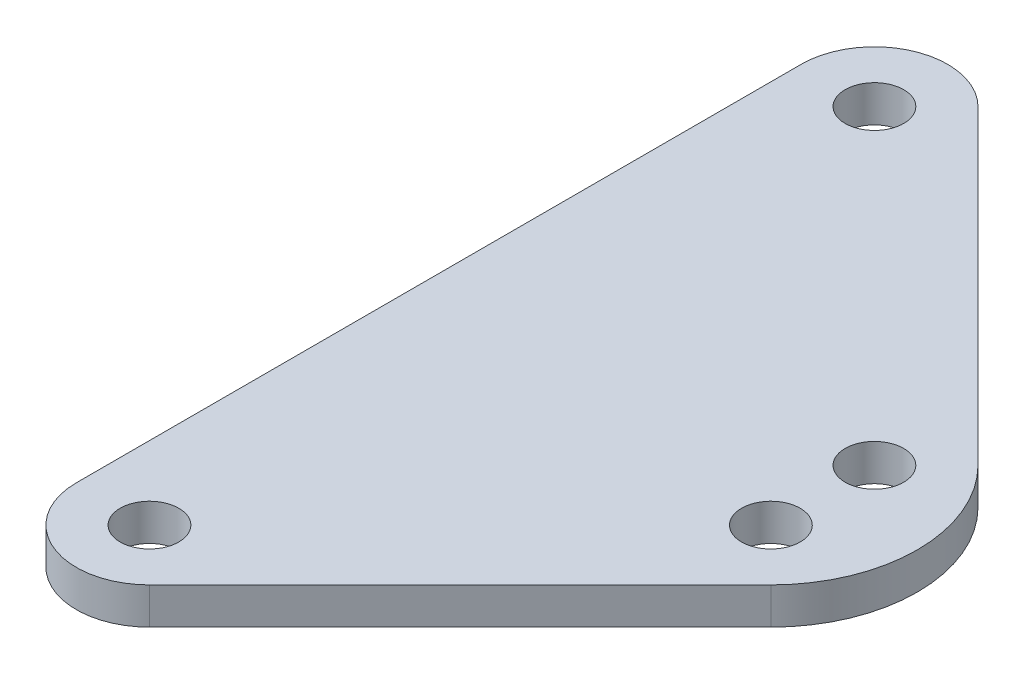
SolidWorks part; units mm, degrees
material "PMMA"
ref_plane "Front Plane" through (0, 0, 0) normal (0, 0, 1) x (1, 0, 0)
ref_plane "Top Plane" through (0, 0, 0) normal (0, 1, 0) x (1, 0, 0)
ref_plane "Right Plane" through (0, 0, 0) normal (1, 0, 0) x (0, 0, -1)
sketch "Sketch1" plane through (0, 0, 0) normal (0, 1, 0) x (1, 0, 0)
  line L0 (34.1421, 34.1421) -> (118.9949, 118.9949)
  line L1 (118.9949, 175.5635) -> (34.1421, 260.4163)
  line L2 (0, 246.2742) -> (0, 48.2843)
  circle A0 centre (20, 48.2843) radius 8
  circle A1 centre (104.8528, 133.1371) radius 8
  circle A2 centre (104.8528, 161.4214) radius 8
  circle A3 centre (20, 246.2742) radius 8
  arc A4 (118.9949, 118.9949) -> (118.9949, 175.5635) centre (90.7107, 147.2792) ccw
  arc A5 (34.1421, 260.4163) -> (0, 246.2742) centre (20, 246.2742) ccw
  arc A6 (34.1421, 34.1421) -> (0, 48.2843) centre (20, 48.2843) cw
  point P12 (-14.5741, 186.8364)
  point P13 (0, 0)
  point P14 (-23.9885, 4.2958)
  point P15 (89.0917, 89.0917)
  point P16 (146.282, 124.0072)
  point P17 (77.7817, 106.066)
  point P18 (60.8643, 123.1235)
  point P19 (105.075, 133.3593)
  point P20 (95.2365, 159.3219)
  point P21 (107.2973, 135.5816)
  point P22 (98.8614, 129.0396)
  point P23 (19.7434, 48.6078)
  point P24 (20.2559, 48.5402)
  point P31 (0, 0)
  dimension "D3" = 16
  dimension "D4" = 16
  dimension "D5" = 16
  dimension "D6" = 16
  dimension "D16" = 40
  dimension "D17" = 20
  dimension "D2" = 40
  dimension "D7" = 120
  dimension "D8" = 120
  dimension "D9" = 20
  dimension "D10" = 45
  dimension "D11" = 20
  dimension "D12" = 20
  dimension "D13" = 20
  dimension "D14" = 40
  dimension "D15" = 20
extrude "Boss-Extrude1" add sketch "Sketch1" along normal blind 10
